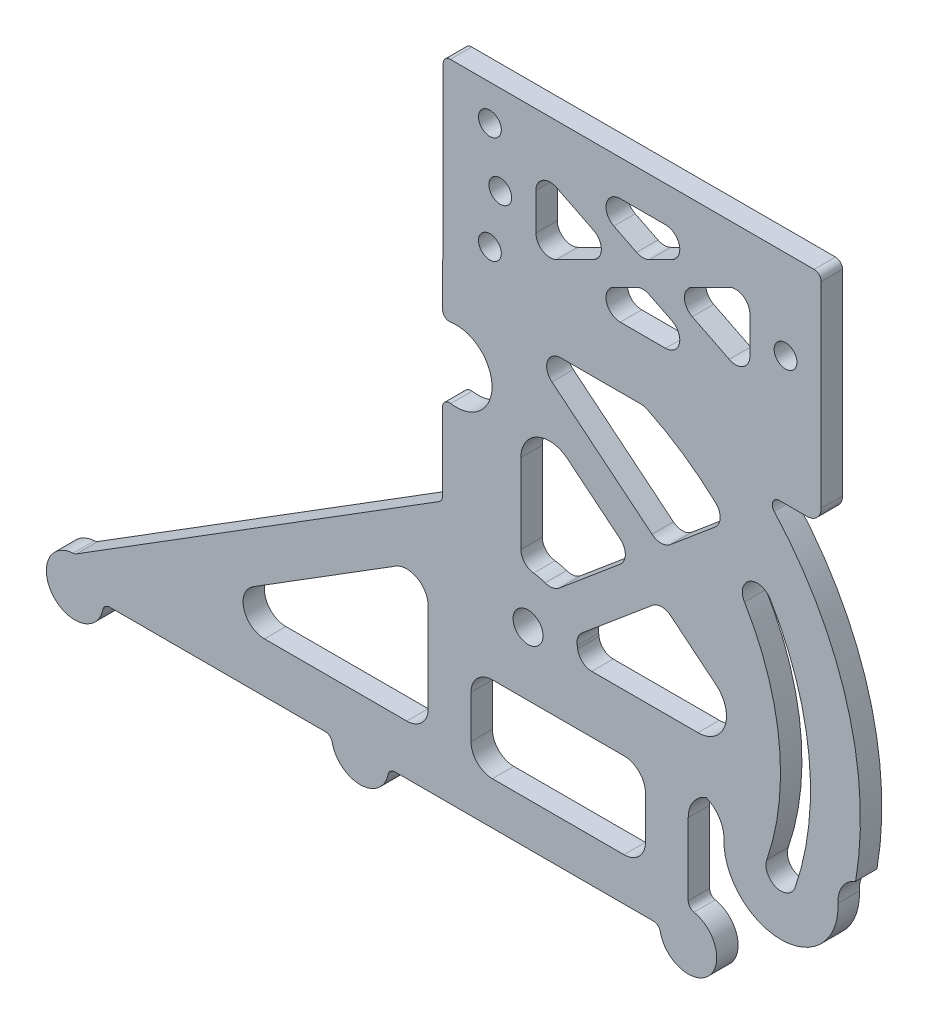
SolidWorks part; units mm, degrees
ref_plane "前视基准面" through (0, 0, 0) normal (0, 0, 1) x (1, 0, 0)
ref_plane "上视基准面" through (0, 0, 0) normal (0, 1, 0) x (1, 0, 0)
ref_plane "右视基准面" through (0, 0, 0) normal (1, 0, 0) x (0, 0, -1)
sketch "草图1" plane through (0, 0, 0) normal (0, 0, 1) x (1, 0, 0)
  line L0 (5.35, -58.5) -> (42.6446, -54.5802) construction
  line L1 (33.55, -61.4) -> (-14.65, -61.4) construction
  line L2 (33.55, -61.4) -> (33.55, -33.5) construction
  line L3 (33.55, -33.5) -> (-14.65, -33.5) construction
  line L4 (-14.65, -61.4) -> (-14.65, -33.5) construction
  line L5 (9.45, -33.5) -> (9.45, -61.4) construction
  line L6 (33.55, -47.45) -> (-14.65, -47.45) construction
  line L7 (5.35, -58.5) -> (37.4938, -39.1861) construction
  line L8 (5.35, -58.5) -> (40.8069, -70.7088) construction
  line L9 (-6.55, 5) -> (-6.55, -20)
  line L10 (-6.55, -20) -> (-6.65, -20)
  line L11 (-6.65, -20) -> (-6.65, -27.2265)
  line L12 (-6.65, -66.4) -> (27.3216, -66.4)
  line L14 (38.2523, -25.5) -> (46.45, -25.5)
  line L15 (46.45, -25.5) -> (46.45, 5)
  line L16 (46.45, 5) -> (-6.55, 5)
  line L17 (-14.65, -33.5) -> (5.35, -58.5) construction
  line L18 (5.35, -58.5) -> (-4.7053, -31.8328) construction
  line L19 (-6.65, -36.4391) -> (-6.65, -66.4)
  line L20 (47.5474, -66.4) -> (51.2755, -66.4)
  line L21 (5.35, -58.5) -> (33.6297, -60.4775) construction
  line L22 (27.3216, -66.4) -> (34.0665, -66.4)
  circle A0 centre (0, 0) radius 1.6
  circle A1 centre (0, -15) radius 1.6
  circle A2 centre (41.45, -7.5) radius 1.6
  circle A3 centre (1.45, -7.5) radius 1.6
  circle A4 centre (5.35, -58.5) radius 2.1
  circle A6 centre (-14.65, -33.5) radius 2.1 construction
  circle A8 centre (33.55, -61.4) radius 2.1 construction
  circle A9 centre (42.6446, -54.5802) radius 2.1 construction
  circle A10 centre (5.35, -58.5) radius 37.5 construction
  arc A11 (39.2938, -38.1045) -> (35.6937, -40.2677) centre (37.4938, -39.1861) ccw
  arc A12 (38.8214, -70.0251) -> (42.7925, -71.3925) centre (40.8069, -70.7088) ccw
  arc A13 (38.8214, -70.0251) -> (35.6937, -40.2677) centre (5.35, -58.5) ccw
  arc A14 (42.7925, -71.3925) -> (39.2938, -38.1045) centre (5.35, -58.5) ccw
  arc A15 (38.2523, -25.5) -> (51.2755, -66.4) centre (5.35, -58.5) cw
  arc A16 (-6.65, -36.4391) -> (-6.65, -27.2265) centre (-4.7053, -31.8328) ccw
  arc A18 (28.6418, -60.1287) -> (27.3216, -66.4) centre (5.35, -58.5) cw construction
  arc A19 (38.6175, -60.8263) -> (37.7495, -66.4) centre (5.35, -58.5) cw construction
  circle A20 centre (5.35, -58.5) radius 28.3487 construction
  arc A21 (38.6175, -60.8263) -> (28.6418, -60.1287) centre (33.6297, -60.4775) ccw construction
  arc A22 (34.0665, -66.4) -> (47.5474, -66.4) centre (40.8069, -70.7088) ccw
  point P12 (9.45, -47.45)
  dimension "D4" = 3.2
  dimension "D13" = 4.2
  dimension "D12" = 75
  dimension "D14" = 4.2
  dimension "D22" = 7
  dimension "D26" = 10
  dimension "D27" = 15
  dimension "D28" = 27.9
  dimension "D29" = 5
  dimension "D32" = 8
  dimension "D1" = 15
  dimension "D2" = 40
  dimension "D3" = 7.5
  dimension "D5" = 1.45
  dimension "D6" = 26
  dimension "D7" = 32
  dimension "D8" = 48.2
  dimension "D9" = 27.9
  dimension "D10" = 25
  dimension "D11" = 20
  dimension "D15" = 25
  dimension "D16" = 25
  dimension "D17" = 5
  dimension "D18" = 5
  dimension "D19" = 8
  dimension "D20" = 5
  dimension "D21" = 5
  dimension "D23" = 18
  dimension "D24" = 12
  dimension "D25" = 18
  dimension "D30" = 6
  dimension "D31" = 28.5
extrude "凸台-拉伸1" add sketch "草图1" along normal blind 3
sketch "草图2" plane through (0, 0, 3) normal (0, 0, 1) x (1, 0, 0)
  line L0 (4.35, -23.5) -> (4.35, -51.5718) construction
  line L1 (36.45, -15) -> (6.45, -15) construction
  line L2 (36.45, -15) -> (36.45, 0) construction
  line L3 (36.45, 0) -> (6.45, 0) construction
  line L4 (6.45, -15) -> (6.45, 0) construction
  line L5 (21.45, 0) -> (21.45, -15) construction
  line L6 (36.45, -7.5) -> (6.45, -7.5) construction
  line L7 (4.35, -23.5) -> (3.5049, -23.5) construction
  line L8 (12.2919, -59.4) -> (40.387, -59.4) construction
  line L9 (-6.65, -36.4391) -> (-6.65, -66.4) construction
  line L10 (-6.65, -66.4) -> (34.0665, -66.4) construction
  line L11 (46.45, 5) -> (-6.55, 5) construction
  line L12 (32.1988, -35.9712) -> (4.6404, -59.0954) construction
  line L13 (8.7517, -52.3821) -> (20.1211, -42.8421)
  line L14 (11.9656, -56.2123) -> (24.0622, -46.0621)
  line L15 (4.35, -23.5) -> (24.0197, -39.5707)
  line L16 (4.35, -29.9567) -> (20.1211, -42.8421)
  line L18 (4.35, -29.9567) -> (4.35, -51.5718)
  line L19 (12.2919, -59.4) -> (40.387, -59.4)
  line L20 (24.0622, -46.0621) -> (40.387, -59.4)
  line L21 (24.0197, -39.5707) -> (30.5234, -34.1135)
  line L22 (27.9608, -42.7908) -> (39.8873, -52.535) construction
  line L23 (27.9608, -42.7908) -> (33.7374, -37.9437) construction
  line L24 (6.45, -15) -> (36.45, 0) construction
  line L25 (6.45, 0) -> (36.45, -15) construction
  line L26 (6.45, -13.3229) -> (18.0959, -7.5)
  line L27 (36.45, -1.6771) -> (24.8041, -7.5)
  line L28 (9.8041, 0) -> (21.45, -5.8229)
  line L29 (6.45, -1.6771) -> (18.0959, -7.5)
  line L30 (36.45, -1.6771) -> (36.45, -13.3229)
  line L31 (33.0959, -15) -> (9.8041, -15)
  line L32 (6.45, -1.6771) -> (6.45, -13.3229)
  line L33 (9.8041, 0) -> (33.0959, 0)
  line L34 (21.45, -5.8229) -> (33.0959, 0)
  line L35 (24.8041, -7.5) -> (36.45, -13.3229)
  line L36 (21.45, -9.1771) -> (9.8041, -15)
  line L37 (21.45, -9.1771) -> (33.0959, -15)
  line L40 (30.5234, -34.1135) -> (33.2503, -31.8254)
  line L41 (4.35, -23.5) -> (21.6276, -23.5)
  arc A0 (12.2919, -59.4) -> (4.35, -51.5718) centre (5.35, -58.5) ccw construction
  arc A1 (40.387, -59.4) -> (3.5049, -23.5) centre (5.35, -58.5) ccw construction
  circle A2 centre (0, -15) radius 1.6 construction
  circle A3 centre (41.45, -7.5) radius 1.6 construction
  circle A4 centre (1.45, -7.5) radius 1.6 construction
  arc A6 (4.35, -51.5718) -> (8.7517, -52.3821) centre (5.35, -58.5) cw
  arc A7 (11.9656, -56.2123) -> (12.2919, -59.4) centre (5.35, -58.5) cw
  arc A8 (30.5234, -34.1135) -> (3.5049, -23.5) centre (5.35, -58.5) ccw construction
  arc A9 (33.7374, -37.9437) -> (39.8873, -52.535) centre (5.35, -58.5) cw construction
  arc A10 (33.2503, -31.8254) -> (21.6276, -23.5) centre (5.35, -58.5) ccw
  arc A11 (51.2755, -66.4) -> (38.2523, -25.5) centre (5.35, -58.5) ccw construction
  point P0 (21.45, -7.5)
  dimension "D3" = 14
  dimension "D7" = 5
  dimension "D9" = 35.0486
  dimension "D14" = 8
  dimension "D1" = 11
  dimension "D2" = 7
  dimension "D4" = 5
  dimension "D5" = 0
  dimension "D6" = 15
  dimension "D8" = 5
  dimension "D10" = 8.5
  dimension "D11" = 40
  dimension "D12" = 5
  dimension "D13" = 5
  dimension "D15" = 3
extrude "切除-拉伸1" cut sketch "草图2" against normal blind 3
fillet "圆角1" radius 2 24 edges at (33.0959, -15, 1.5) (21.45, -9.1771, 1.5) (36.45, -1.6771, 1.5) (24.8041, -7.5, 1.5) (36.45, -13.3229, 1.5) (33.0959, 0, 1.5) (9.8041, 0, 1.5) (21.45, -5.8229, 1.5) (6.45, -13.3229, 1.5) (18.0959, -7.5, 1.5) (6.45, -1.6771, 1.5) (12.2919, -59.4, 1.5) (24.0622, -46.0621, 1.5) (11.9656, -56.2123, 1.5) (8.7517, -52.3821, 1.5) (20.1211, -42.8421, 1.5) (4.35, -51.5718, 1.5) (46.45, -25.5, 1.5) (-6.55, -20, 1.5) (9.8041, -15, 1.5) (24.0197, -39.5707, 1.5) (33.2503, -31.8254, 1.5) (21.6276, -23.5, 1.5) (4.35, -23.5, 1.5)
fillet "圆角3" radius 1 6 edges at (-6.65, -36.4391, 1.5) (-6.65, -27.2265, 1.5) (-6.65, -20, 1.5) (46.45, 5, 1.5) (38.2523, -25.5, 1.5) (-6.55, 5, 1.5)
fillet "圆角4" radius 4 2 edges at (4.35, -29.9567, 1.5) (40.387, -59.4, 1.5)
sketch "草图3" plane through (0, 0, 3) normal (0, 0, 1) x (1, 0, 0)
  line L0 (27.8069, -81.4) -> (27.8069, -66.4)
  line L1 (-6.65, -66.4) -> (34.0665, -66.4) construction
  line L3 (-6.65, -66.4) -> (27.8069, -66.4)
  line L4 (-14.1931, -85.4) -> (23.8069, -85.4)
  line L5 (-54.1931, -85.4) -> (-22.1931, -85.4)
  line L6 (-58.1931, -81.4) -> (-6.65, -49.1923)
  line L7 (-6.65, -37.758) -> (-6.65, -66.4) construction
  line L8 (-6.65, -49.1923) -> (-6.65, -66.4)
  line L9 (-8.65, -57.5171) -> (-42.0696, -78.4)
  line L10 (-42.0696, -78.4) -> (-8.65, -78.4)
  line L11 (-8.65, -78.4) -> (-8.65, -57.5171)
  line L12 (-2.65, -67.4) -> (-2.65, -79.4)
  line L13 (-2.65, -79.4) -> (21.8069, -79.4)
  line L14 (21.8069, -79.4) -> (21.8069, -67.4)
  line L15 (21.8069, -67.4) -> (-2.65, -67.4)
  arc A0 (23.8069, -85.4) -> (27.8069, -81.4) centre (27.8069, -85.4) ccw
  arc A1 (-22.1931, -85.4) -> (-14.1931, -85.4) centre (-18.1931, -85.4) ccw
  arc A3 (38.8214, -70.0251) -> (42.7925, -71.3925) centre (40.8069, -70.7088) ccw construction
  arc A4 (-58.1931, -81.4) -> (-54.1931, -85.4) centre (-58.1931, -85.4) ccw
  dimension "D1" = 8
  dimension "D3" = 13
  dimension "D2" = 19
  dimension "D4" = 46
  dimension "D5" = 40
  dimension "D6" = 32
  dimension "D7" = 1
  dimension "D8" = 6
  dimension "D9" = 6
  dimension "D10" = 6
  dimension "D11" = 2
  dimension "D12" = 7
  dimension "D13" = 6
extrude "凸台-拉伸2" add sketch "草图3" against normal up to surface (3 mm away) up to face at (20.3345, -54.5487, 0)
fillet "圆角7" radius 3 7 edges at (21.8069, -67.4, 1.5) (21.8069, -79.4, 1.5) (-2.65, -79.4, 1.5) (-2.65, -67.4, 1.5) (-8.65, -78.4, 1.5) (-42.0696, -78.4, 1.5) (-8.65, -57.5171, 1.5)
fillet "圆角8" radius 1 7 edges at (-6.65, -49.1923, 1.5) (-58.1931, -81.4, 1.5) (27.8069, -81.4, 1.5) (23.8069, -85.4, 1.5) (-22.1931, -85.4, 1.5) (-14.1931, -85.4, 1.5) (-54.1931, -85.4, 1.5)
fillet "圆角9" radius 4 3 edges at (27.8069, -66.4, 1.5) (34.0665, -66.4, 1.5) (47.5474, -66.4, 1.5)
